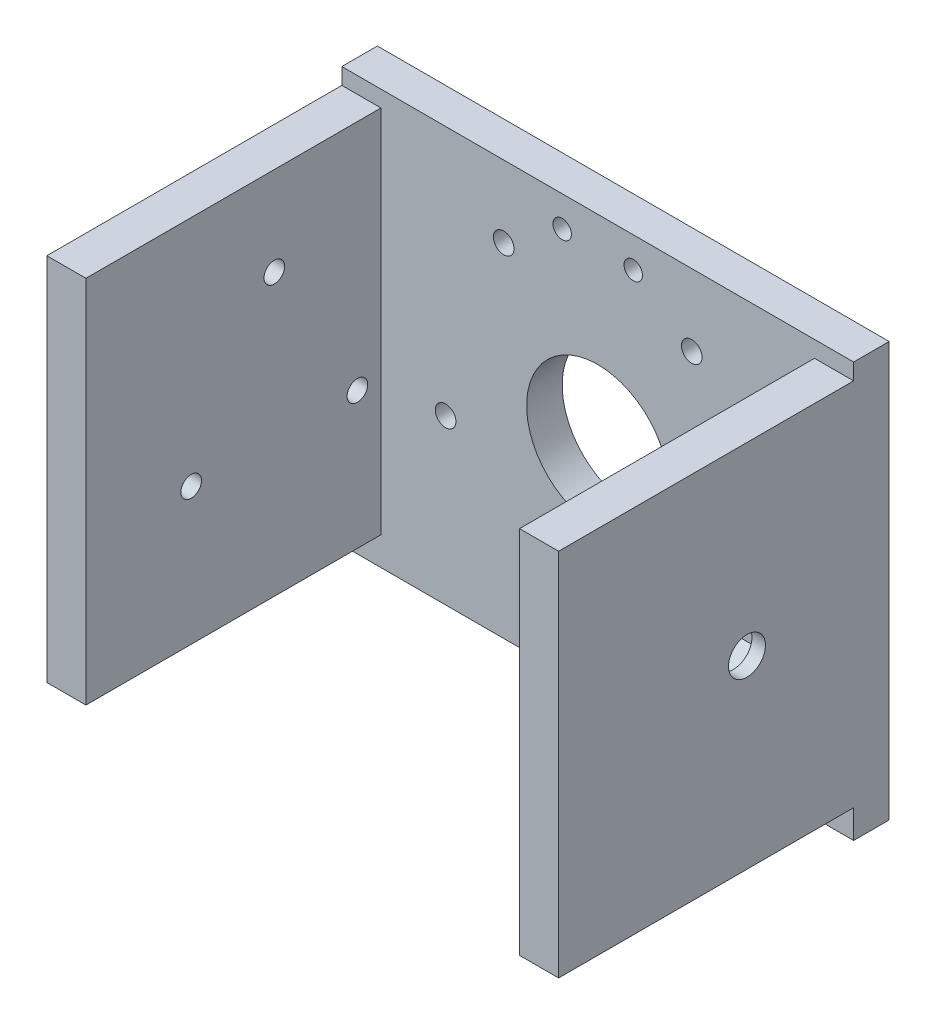
SolidWorks part; units mm, degrees
ref_plane "Front Plane" through (0, 0, 0) normal (0, 0, 1) x (1, 0, 0)
ref_plane "Top Plane" through (0, 0, 0) normal (0, 1, 0) x (1, 0, 0)
ref_plane "Right Plane" through (0, 0, 0) normal (1, 0, 0) x (0, 0, -1)
ref_plane "Plane1" through (0, 0, 280) normal (0, 0, 1) x (1, 0, 0)
sketch "Sketch1" plane through (0, 0, 280) normal (0, 0, 1) x (1, 0, 0)
  line L0 (264, 270) -> (336, 270)
  line L1 (336, 270) -> (336, 328.3)
  line L2 (336, 328.3) -> (264, 328.3)
  line L3 (264, 328.3) -> (264, 270)
  circle A0 centre (300, 300) radius 10
  circle A1 centre (286.7748, 318.2029) radius 1.45
  circle A2 centre (278.6012, 293.0471) radius 1.45
  circle A3 centre (300, 277.5) radius 1.45
  circle A4 centre (321.3988, 293.0471) radius 1.45
  circle A5 centre (313.2252, 318.2029) radius 1.45
  circle A6 centre (295, 324) radius 1.3
  circle A7 centre (305, 324) radius 1.3
extrude "Boss-Extrude1" add sketch "Sketch1" along normal blind 5
ref_plane "Plane2" through (264, 0, 0) normal (1, 0, 0) x (0, 0, -1)
sketch "Sketch2" plane through (264, 0, 0) normal (1, 0, 0) x (0, 0, -1)
  line L0 (-280, 274) -> (-326.5, 274)
  line L1 (-326.5, 274) -> (-326.5, 326)
  line L2 (-326.5, 326) -> (-280, 326)
  line L3 (-280, 326) -> (-280, 274)
  circle A0 centre (-300, 313.5) radius 1.45
  circle A1 centre (-288.3087, 293.25) radius 1.45
  circle A2 centre (-311.6913, 293.25) radius 1.45
extrude "Boss-Extrude2" add sketch "Sketch2" along normal blind 5.5
sketch "Sketch3" plane through (264, 0, 0) normal (1, 0, 0) x (0, 0, -1)
  circle A0 centre (-300, 300) radius 7.6
extrude "Cut-Extrude1" cut sketch "Sketch3" along normal blind 1.2
ref_plane "Plane3" through (330.5, 0, 0) normal (1, 0, 0) x (0, 0, -1)
sketch "Sketch4" plane through (330.5, 0, 0) normal (1, 0, 0) x (0, 0, -1)
  line L0 (-280, 274) -> (-326.5, 274)
  line L1 (-326.5, 274) -> (-326.5, 326)
  line L2 (-326.5, 326) -> (-280, 326)
  line L3 (-280, 326) -> (-280, 274)
  circle A0 centre (-300, 300) radius 2.6
extrude "Boss-Extrude3" add sketch "Sketch4" along normal blind 5.5
sketch "Sketch5" plane through (330.5, 0, 0) normal (1, 0, 0) x (0, 0, -1)
  line L0 (-304.1, 302.3671) -> (-300, 304.7343)
  line L1 (-300, 304.7343) -> (-295.9, 302.3671)
  line L2 (-295.9, 302.3671) -> (-295.9, 297.6329)
  line L3 (-295.9, 297.6329) -> (-300, 295.2657)
  line L4 (-300, 295.2657) -> (-304.1, 297.6329)
  line L5 (-304.1, 297.6329) -> (-304.1, 302.3671)
extrude "Cut-Extrude2" cut sketch "Sketch5" along normal blind 3.6
ref_plane "Plane4" through (300, 0, 0) normal (1, 0, 0) x (0, 0, -1)
ref_plane "Plane5" through (0, 300, 0) normal (0, 1, 0) x (1, 0, 0)
ref_axis "HIP_AXIS" through (300, 300, 328.825) along (0, 0, -1)
ref_plane "Plane6" through (0, 0, 300) normal (0, 0, 1) x (1, 0, 0)
ref_axis "ABAD_AXIS" through (339.6, 300, 300) along (-1, 0, 0)
